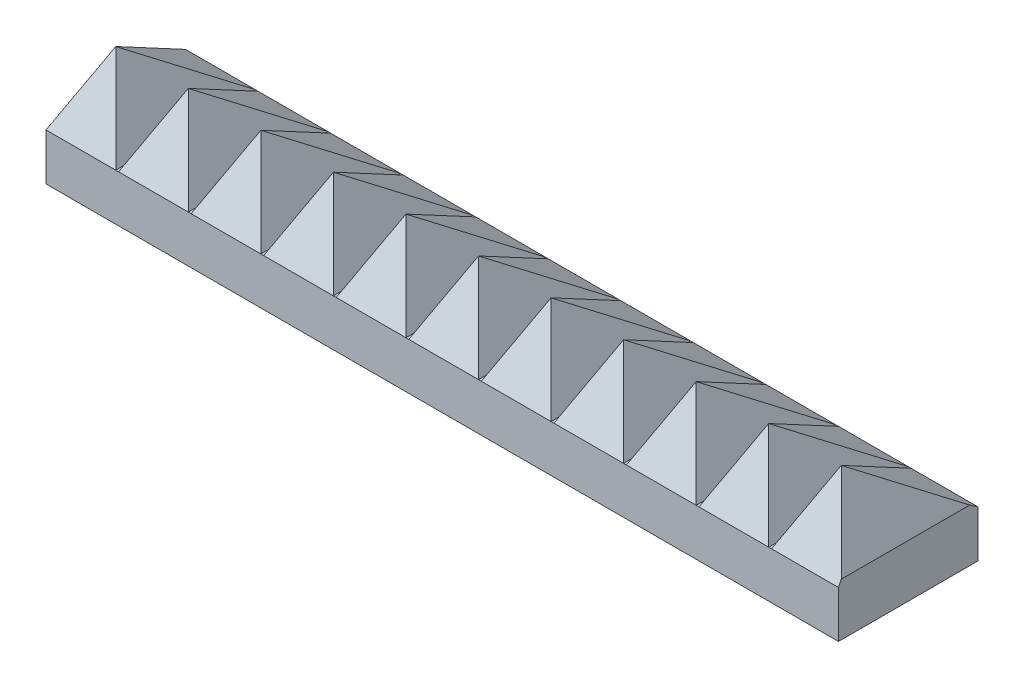
SolidWorks part; units mm, degrees
ref_plane "Front Plane" through (0, 0, 0) normal (0, 0, 1) x (1, 0, 0)
ref_plane "Top Plane" through (0, 0, 0) normal (0, 1, 0) x (1, 0, 0)
ref_plane "Right Plane" through (0, 0, 0) normal (1, 0, 0) x (0, 0, -1)
sketch "Sketch1" plane through (0, 0, 0) normal (0, 1, 0) x (1, 0, 0)
  line L1 (0, 0) -> (19.05, 0)
  line L2 (0, 0) -> (0, -19.05)
  line L3 (0, -19.05) -> (19.05, -19.05)
  line L4 (19.05, 0) -> (19.05, -19.05)
extrude "Boss-Extrude2" add sketch "Sketch1" along normal blind 6.35
ref_plane "Plane2" through (0, 26.0731, 0) normal (0, 1, 0) x (1, 0, 0)
sketch "Sketch8" plane through (0, 0, 0) normal (0, 1, 0) x (1, 0, 0)
  line L9 (0, 9.525) -> (217.17, 9.525)
  line L10 (0, 9.525) -> (0, -28.575)
  line L11 (0, -28.575) -> (217.17, -28.575)
  line L12 (217.17, 9.525) -> (217.17, -28.575)
extrude "Boss-Extrude4" add sketch "Sketch8" along normal blind 6.35 contours L11 L12 L9 L10
extrude "Boss-Extrude5" add sketch "Sketch8<5>" against normal blind 6.4262 contours L11 L12 L9 L10
sketch "Sketch8<5>" plane through (0, 0, 0) normal (0, 1, 0) x (1, 0, 0) same geometry as "Sketch8"
sketch "Sketch9" plane through (0, 6.35, 0) normal (0, 1, 0) x (1, 0, 0)
  line L0 (0, -28.575) -> (217.17, -28.575) construction
  line L1 (0, 9.525) -> (19.05, 9.525)
  line L2 (0, 9.525) -> (0, -28.575)
  line L3 (0, -28.575) -> (19.05, -28.575)
  line L4 (19.05, 9.525) -> (19.05, -28.575)
sketch "Sketch13" plane through (0, 6.35, 0) normal (0, 1, 0) x (1, 0, 0)
  line L0 (0, -9.525) -> (19.05, -28.575)
  line L1 (0, 9.525) -> (0, -28.575) construction
  line L2 (19.05, -28.575) -> (19.05, -9.525)
  line L3 (19.05, 9.525) -> (19.05, -28.575) construction
  line L4 (19.05, -9.525) -> (0, -28.575)
ref_plane "Plane4" through (0, 26.0731, 0) normal (0, 1, 0) x (1, 0, 0)
sketch "Sketch14" plane through (0, 26.0731, 0) normal (0, 1, 0) x (1, 0, 0)
  line L0 (0, -9.525) -> (19.05, -28.575) construction
  point P0 (9.525, -19.05)
loft "Loft3" add profiles "Sketch9", "Sketch14"
pattern_linear "LPattern3" count 11 spacing 19.812 along (1, 0, 0) of "Loft3"
sketch "Sketch15" plane through (0, -6.4262, 0) normal (0, -1, 0) x (1, 0, 0)
  line L0 (217.17, -9.525) -> (217.17, 28.575) construction
  line L1 (0, -9.525) -> (0, 28.575) construction
  circle A0 centre (179.07, 9.525) radius 12.192
  circle A1 centre (38.1, 9.525) radius 12.192
  circle A2 centre (108.585, 9.525) radius 12.192
  dimension "D1" = 38.1
  dimension "D2" = 70.485
  dimension "D3" = 38.1
  dimension "D4" = 24.384
  dimension "D5" = 24.384
  dimension "D6" = 24.384
extrude "Boss-Extrude6" add sketch "Sketch15" along normal blind 6.35
ref_plane "Plane5" through (219.71, 0, 0) normal (1, 0, 0) x (0, 0, -1)
sketch "Sketch16" plane through (219.71, 0, 0) normal (1, 0, 0) x (0, 0, -1)
  line L1 (-28.575, -6.4262) -> (9.525, -6.4262)
  line L2 (-28.575, -6.4262) -> (-28.575, 15.6471)
  line L3 (-28.575, 15.6471) -> (9.525, 15.6471)
  line L4 (9.525, -6.4262) -> (9.525, 15.6471)
extrude "Cut-Extrude1" cut sketch "Sketch16" against normal blind 3.302 contours L3 L4 L1 L2
